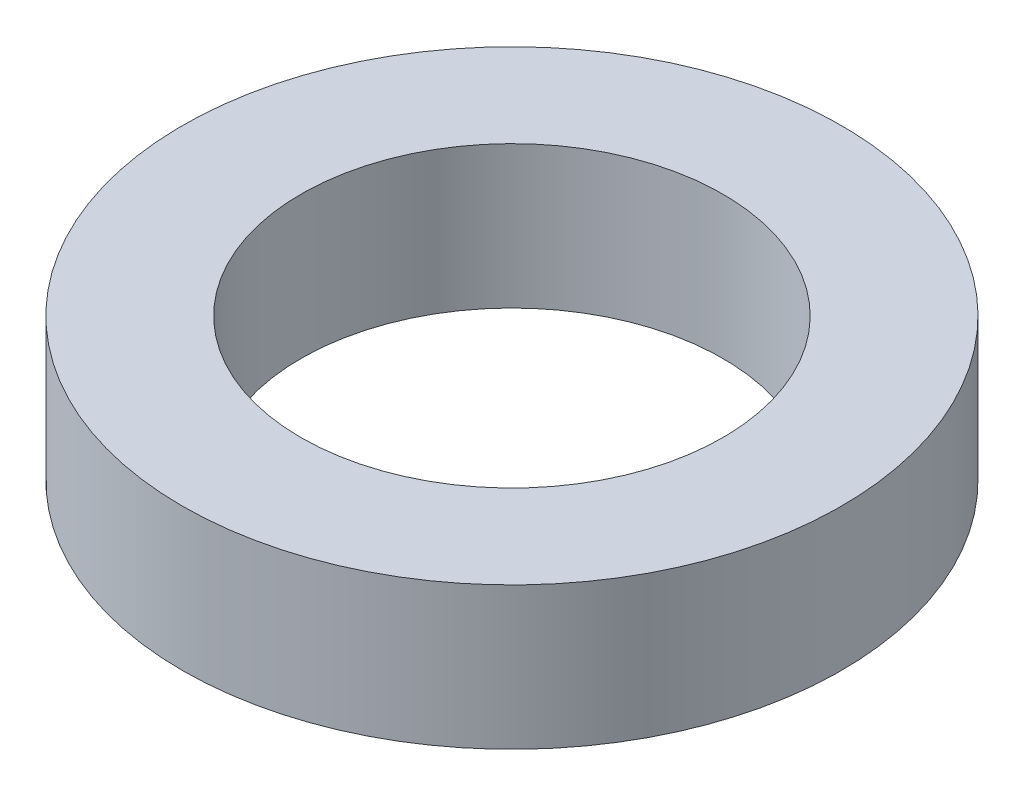
SolidWorks part; units mm, degrees
ref_plane "Front Plane" through (0, 0, 0) normal (0, 0, 1) x (1, 0, 0)
ref_plane "Top Plane" through (0, 0, 0) normal (0, 1, 0) x (1, 0, 0)
ref_plane "Right Plane" through (0, 0, 0) normal (1, 0, 0) x (0, 0, -1)
sketch "Sketch1" plane through (0, 0, 0) normal (0, 1, 0) x (1, 0, 0)
  circle A0 centre (0, 0) radius 62.5
  dimension "FLANGE_OD" = 125
extrude "Boss-Extrude1" add sketch "Sketch1" along normal blind 27
sketch "Sketch2" plane through (0, 0, 0) normal (0, 1, 0) x (1, 0, 0)
  circle A0 centre (0, 0) radius 40
  dimension "BORE_D" = 80
extrude "Cut-Extrude1" cut sketch "Sketch2" along normal through all
sketch "Sketch3" plane through (0, 27, 0) normal (0, 1, 0) x (1, 0, 0)
  circle A0 centre (0, 0) radius 25.6337 construction
  circle A1 centre (-25.6337, 0) radius 3.3244
  dimension "BOLT_D" = 6.6488
  dimension "BOLT_PCD" = 51.2674
extrude "Cut-Extrude2" cut sketch "Sketch3" against normal blind 18.5322 rebuild error yes
pattern_circular "CirPattern1" count 4 over 360 rebuild error yes
